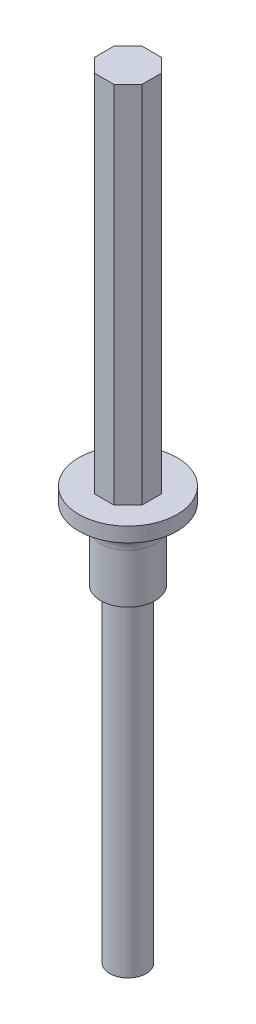
SolidWorks part; units mm, degrees
ref_plane "Front Plane" through (0, 0, 0) normal (0, 0, 1) x (1, 0, 0)
ref_plane "Top Plane" through (0, 0, 0) normal (0, 1, 0) x (1, 0, 0)
ref_plane "Right Plane" through (0, 0, 0) normal (1, 0, 0) x (0, 0, -1)
sketch "Sketch1" plane through (0, 0, 0) normal (0, 1, 0) x (1, 0, 0)
  circle A0 centre (0, 0) radius 2.5
  dimension "D1" = 5
extrude "Boss-Extrude1" add sketch "Sketch1" against normal blind 42.45 and the other way blind 2.5
sketch "Sketch2" plane through (0, 2.5, 0) normal (0, 1, 0) x (1, 0, 0)
  circle A0 centre (0, 0) radius 3.75
  circle A1 centre (0, 0) radius 2.5 construction
  point P3 (-1.5486, -3.129)
  point P6 (-25.0145, 5.8908)
  dimension "D1" = 7.5
extrude "Boss-Extrude2" add sketch "Sketch2" along normal up to surface (11.7549 mm away) separate body
sketch "Sketch3" plane through (0, 14.2549, 0) normal (0, 1, 0) x (1, 0, 0)
  line L1 (-3.2336, -1.3394) -> (-1.3394, -3.2336)
  line L2 (-1.3394, -3.2336) -> (1.3394, -3.2336)
  line L3 (1.3394, -3.2336) -> (3.2336, -1.3394)
  line L4 (3.2336, -1.3394) -> (3.2336, 1.3394)
  line L5 (3.2336, 1.3394) -> (1.3394, 3.2336)
  line L6 (1.3394, 3.2336) -> (-1.3394, 3.2336)
  line L7 (-1.3394, 3.2336) -> (-3.2336, 1.3394)
  line L8 (-3.2336, 1.3394) -> (-3.2336, -1.3394)
  circle A0 centre (0, 0) radius 3.5 construction
  circle A1 centre (0, 0) radius 3.75 construction
  point P1 (0, 0)
  point P12 (-23.3731, 11.1213)
  point P15 (-1.5486, -3.129)
  point P16 (0, 0)
  point P19 (-21.6639, 13.267)
  dimension "D1" = 7
extrude "Boss-Extrude3" add sketch "Sketch3" along normal blind 50 separate body
sketch "Sketch4" plane through (0, 14.2549, 0) normal (0, 1, 0) x (1, 0, 0)
  circle A0 centre (0, 0) radius 6.75
  circle A1 centre (0, 0) radius 3.75 construction
  dimension "D1" = 3
extrude "Boss-Extrude4" add sketch "Sketch4" against normal blind 2 contours A0
fillet "Fillet1" radius 3 1 edges at (0, 12.2549, 3.75)
